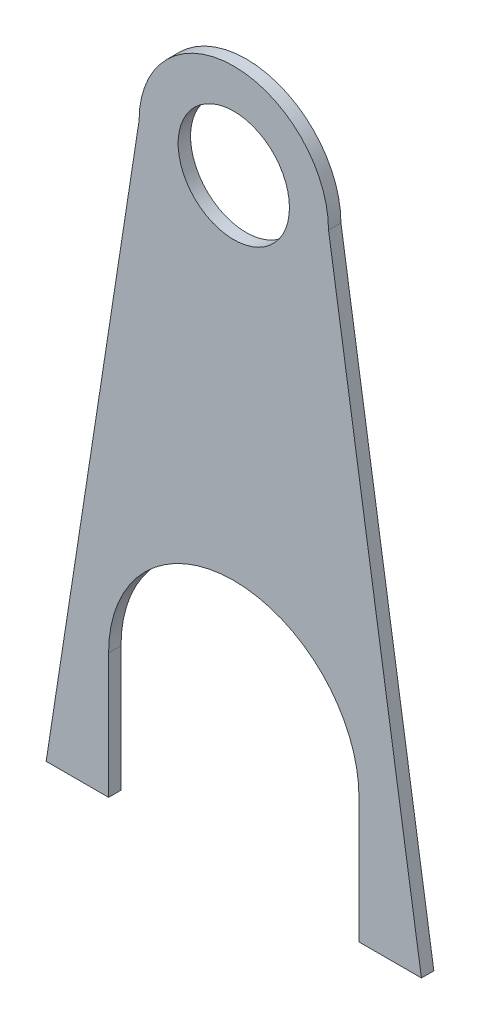
SolidWorks part; units mm, degrees
ref_plane "Front Plane" through (0, 0, 0) normal (0, 0, 1) x (1, 0, 0)
ref_plane "Top Plane" through (0, 0, 0) normal (0, 1, 0) x (1, 0, 0)
ref_plane "Right Plane" through (0, 0, 0) normal (1, 0, 0) x (0, 0, -1)
sketch "Sketch1" plane through (0, 0, 0) normal (0, 0, 1) x (1, 0, 0)
  line L0 (-24.2161, 0) -> (24.2161, 0) construction
  line L1 (0, 0) -> (0, -153.67) construction
  line L2 (47.961, -153.67) -> (-47.961, -153.67)
  line L3 (-47.961, -153.67) -> (-24.2161, 0)
  line L4 (24.2161, 0) -> (47.961, -153.67)
  arc A0 (-24.2161, 0) -> (24.2161, 0) centre (0, 0) cw
  circle A1 centre (0, 0) radius 14.224
  point P8 (0, -153.67)
  dimension "D1" = 28.448
  dimension "D2" = 153.67
extrude "Boss-Extrude1" add sketch "Sketch1" along normal blind 3.175
sketch "Sketch2" plane through (0, 0, 3.175) normal (0, 0, 1) x (1, 0, 0)
  line L0 (0, 0) -> (0, -153.67) construction
  line L1 (-47.961, -153.67) -> (47.961, -153.67) construction
  line L2 (32.004, -121.666) -> (32.004, -153.67)
  line L3 (-32.004, -121.666) -> (-32.004, -153.67)
  line L4 (32.004, -121.666) -> (-32.004, -121.666) construction
  line L5 (32.004, -153.67) -> (-32.004, -153.67)
  arc A1 (-32.004, -121.666) -> (32.004, -121.666) centre (0, -121.666) cw
  point P11 (0, -89.662)
  line M5 (-47.961, -153.67) -> (47.961, -153.67)
  dimension "D1" = 64.008
  dimension "D2" = 64.008
extrude "Cut-Extrude1" cut sketch "Sketch2" against normal up to surface (3.175 mm away) contours A1 L3 L2 M5 region at (0, -124.6536, 3.175) up to face at (0, -70.781, 0)
